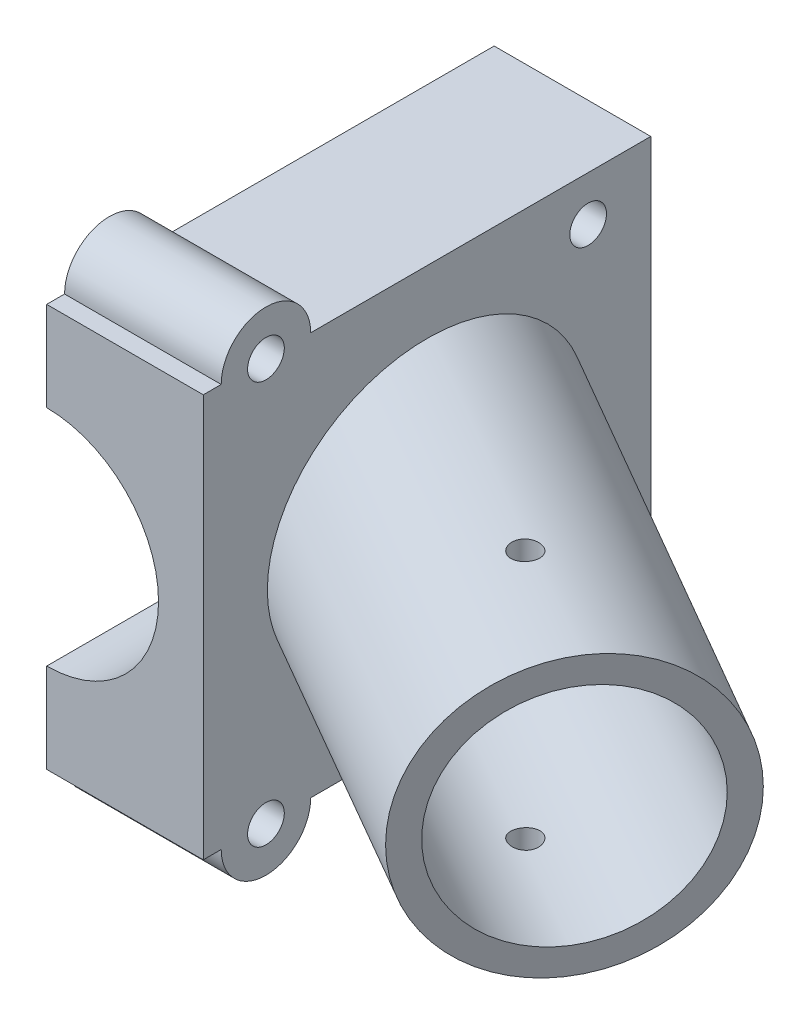
SolidWorks part; units mm, degrees
material "PLA"
ref_plane "Front Plane" through (0, 0, 0) normal (0, 0, 1) x (1, 0, 0)
ref_plane "Top Plane" through (0, 0, 0) normal (0, 1, 0) x (1, 0, 0)
ref_plane "Right Plane" through (0, 0, 0) normal (1, 0, 0) x (0, 0, -1)
sketch "Sketch1" plane through (0, 0, 0) normal (0, 0, 1) x (1, 0, 0)
  line L0 (-17.5, 22.5) -> (-17.5, 0)
  line L1 (55, 0) -> (-55, 0) construction
  line L2 (-17.5, 0) -> (17.5, 0)
  line L3 (17.5, 0) -> (17.5, 22.5)
  line L4 (-17.5, 22.5) -> (-12.5, 22.5)
  line L5 (17.5, 22.5) -> (12.5, 22.5)
  line L6 (0, -44.7868) -> (0, 44.7868) construction
  arc A0 (-12.5, 22.5) -> (12.5, 22.5) centre (0, 22.5) ccw
  dimension "D1" = 12.5
  dimension "D2" = 22.5
  dimension "D3" = 5
extrude "Boss-Extrude1" add sketch "Sketch1" along normal mid plane 50
sketch "Construct1" plane through (0, 0, 0) normal (0, 1, 0) x (1, 0, 0)
  line L0 (17.5, 0) -> (43.4808, -15) construction
  line L1 (-44.2539, 0) -> (44.2539, 0) construction
  line L2 (34.7051, -0.1998) -> (26.2756, -14.8002) construction
  line L3 (17.5, -25) -> (17.5, 25) construction
  point P6 (30.4904, -7.5)
  point P7 (30.4904, -7.5)
  dimension "D1" = 30
  dimension "D2" = 15
ref_plane "LegBuildPlane" through (26.1154, 0, 15.0777) normal (0.866, 0, 0.5) x (0.5, 0, -0.866)
sketch "Sketch5" plane through (26.1154, 0, 15.0777) normal (0.866, 0, 0.5) x (0.5, 0, -0.866)
  line L0 (-6.7, 22.5) -> (-3.75, 22.5)
  line L1 (21.25, 22.5) -> (24.2, 22.5)
  line L2 (17.1795, 0) -> (0.3205, 0) construction
  arc A0 (-3.75, 22.5) -> (21.25, 22.5) centre (8.75, 22.5) ccw
  arc A1 (-6.7, 22.5) -> (24.2, 22.5) centre (8.75, 22.5) ccw
  point P9 (8.75, 0)
  dimension "D1" = 15.45
  dimension "D2" = 12.5
  dimension "D3" = 22.5
  dimension "D4" = 0
extrude "Boss-Extrude2" add sketch "Sketch5" against normal up to surface and the other way blind 30 up to face at (17.5, 11.25, 0)
sketch "Sketch9" plane through (-17.5, 0, 0) normal (-1, 0, 0) x (0, 0, 1)
  line L2 (55, 0) -> (-55, 0) construction
  line L3 (-25, 22.5) -> (-25, 0) construction
  circle A0 centre (-18, 5) radius 2.05
  dimension "D3" = 5
  dimension "D1" = 4.1
  dimension "D4" = 7
extrude "Cut-Extrude3" cut sketch "Sketch9" against normal up to surface (35 mm away) up to face at (17.5, 12.425, 0)
sketch "Construct2" plane through (0, 22.5, 0) normal (0, 1, 0) x (1, 0, 0)
  line L0 (20.0981, -15.9338) -> (32.5981, 5.7169) construction
  line L2 (50.2211, -33.3253) -> (17.5, -14.4338) construction
  line L3 (62.7211, -11.6747) -> (17.5, 14.4338) construction
  line L4 (17.5, 0) -> (26.3481, -5.1084) construction
  line L11 (-44.2539, 0) -> (44.2539, 0) construction
  dimension "D1" = 3
  dimension "D2" = 90
ref_plane "LegBuildPlane2" through (21.9731, 0, 12.6862) normal (0.866, 0, 0.5) x (0.5, 0, -0.866)
sketch "Sketch12" plane through (21.9731, 0, 12.6862) normal (0.866, 0, 0.5) x (0.5, 0, -0.866)
  line L0 (-3.75, 22.5) -> (21.25, 22.5)
  arc A0 (-3.75, 22.5) -> (21.25, 22.5) centre (8.75, 22.5) ccw
extrude "Boss-Extrude5" add sketch "Sketch12" against normal up to surface (17.4338 mm away) up to face at (17.5, 16.25, 0)
mirror "Mirror1" about plane through (17.5, 22.5, 25) normal (0, -1, 0) of "Boss-Extrude2", "Boss-Extrude1", "Cut-Extrude3", "Boss-Extrude5"
sketch "Sketch13" plane through (0, 0, 0) normal (0, 1, 0) x (1, 0, 0)
  line L0 (17.5, 0) -> (43.4808, -15) construction
  line L1 (48.7461, -35.8801) -> (64.1961, -9.1199) construction
  circle A0 centre (43.4808, -15) radius 1.55
  dimension "D2" = 3.1
  dimension "D1" = 15
extrude "Cut-Extrude4" cut sketch "Sketch13" along normal through all
sketch "Sketch16" plane through (0, 0, 0) normal (1, 0, 0) x (0, 0, -1)
  line L0 (55, 0) -> (-55, 0) construction
  line L1 (25, 45) -> (-25, 45)
  line L2 (25, 45) -> (25, 0)
  line L3 (25, 0) -> (-25, 0)
  line L4 (-25, 45) -> (-25, 0)
  line L5 (-25, 45) -> (-25, 0) construction
extrude "Cut-Extrude5" cut sketch "Sketch16" against normal up to surface (17.5 mm away) up to face at (-17.5, 40, -15.95)
sketch "Sketch18" plane through (0, 0, 0) normal (-1, 0, 0) x (0, 0, 1)
  line L0 (55, 0) -> (-55, 0) construction
  line L2 (13, 0) -> (23, 0)
  arc A0 (23, 0) -> (13, 0) centre (18, 0) cw
  circle A3 centre (-18, 5) radius 2.05 construction
  dimension "D3" = 5
  dimension "D1" = 36
extrude "Boss-Extrude6" add sketch "Sketch18" against normal blind 17.5
sketch "Sketch20" plane through (0, 0, 0) normal (-1, 0, 0) x (0, 0, 1)
  circle A0 centre (18, 0) radius 2.05
  dimension "D1" = 4.1
extrude "Cut-Extrude6" cut sketch "Sketch20" against normal up to surface (17.5 mm away) up to face at (17.5, 40, -15.95)
ref_plane "HolePlane" through (0, 22.5, 0) normal (0, 1, 0) x (1, 0, 0)
mirror "Mirror2" about plane through (0, 22.5, 0) normal (0, 1, 0) of "Boss-Extrude6", "Cut-Extrude6"
equation "\"TubeDiam\"= 12.5"
equation "\"D1@Sketch1\"=\"TubeDiam\""
equation "\"D2@Sketch1\"=\"ClampHeight\""
equation "\"MountLength\"= 50"
equation "\"D1@Boss-Extrude1\"=\"MountLength\""
equation "\"MountHoleSize\"=3.1"
equation "\"LipWidth\"= 5"
equation "\"D3@Sketch1\"=\"LipWidth\""
equation "\"LegDiam\"= 12.5"
equation "\"LegThickness\"= \"TubeDiam\" + 2.95"
equation "\"D1@Sketch5\"=\"LegThickness\""
equation "\"D2@Sketch5\"=\"TubeDiam\""
equation "\"ClampHeight\" = \"TubeDiam\" + 10"
equation "\"D3@Sketch5\"=\"ClampHeight\""
equation "\"HubHoleDist\"=7"
equation "\"HubHoleSize\"=4.1"
equation "\"D2@Sketch13\"=\"MountHoleSize\""
equation "\"D1@Sketch9\"=\"HubHoleSize\""
equation "\"D4@Sketch9\"=\"HubHoleDist\""
equation "\"D1@Sketch18\"=\"MountLength\" - 2 * \"HubHoleDist\""
equation "\"D1@Boss-Extrude6\"=\"TubeDiam\" +5"
equation "\"D1@Sketch20\"=\"HubHoleSize\""
